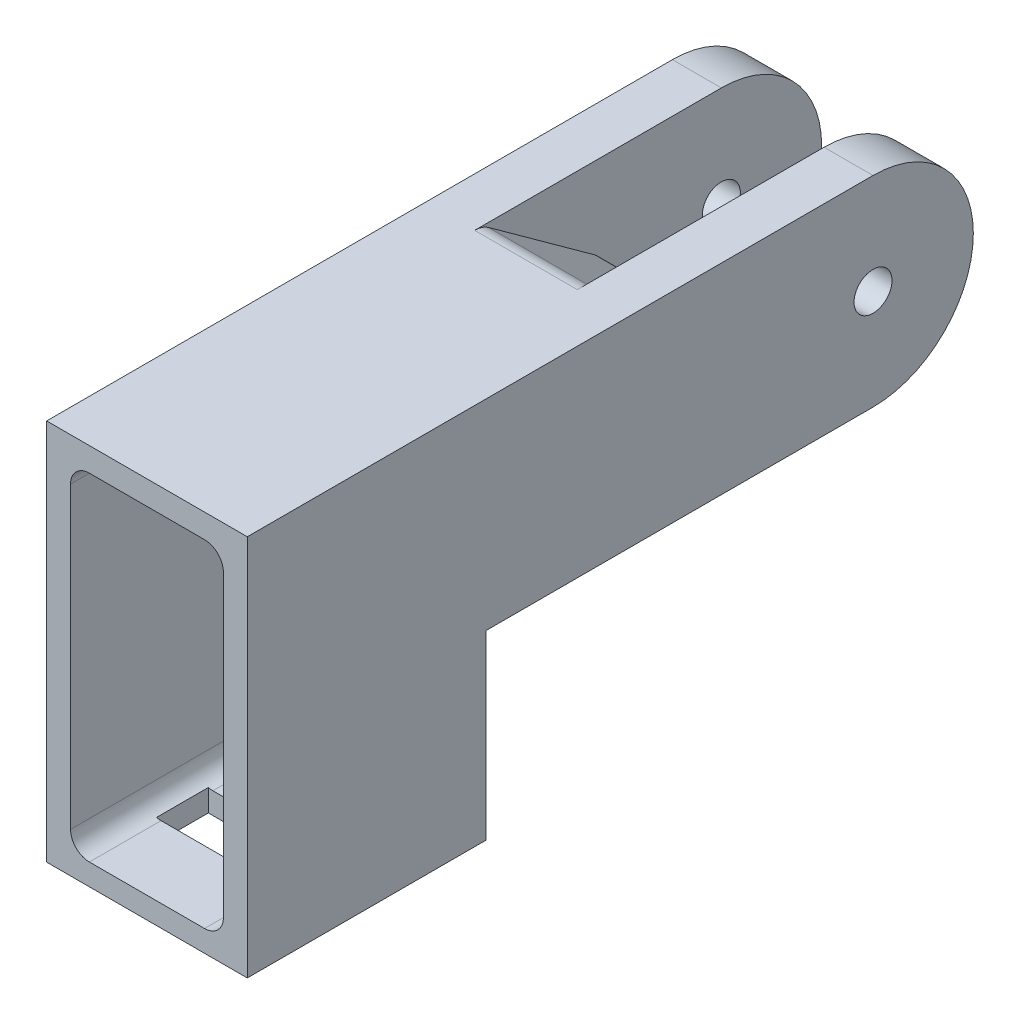
SolidWorks part; units mm, degrees
ref_plane "Front Plane" through (0, 0, 0) normal (0, 0, 1) x (1, 0, 0)
ref_plane "Top Plane" through (0, 0, 0) normal (0, 1, 0) x (1, 0, 0)
ref_plane "Right Plane" through (0, 0, 0) normal (1, 0, 0) x (0, 0, -1)
sketch "Sketch2" plane through (0, 0, 0) normal (0, 0, 1) x (1, 0, 0)
  line L1 (-21, 21) -> (21, 21)
  line L2 (-21, 21) -> (-21, -21)
  line L3 (-21, -21) -> (21, -21)
  line L4 (21, 21) -> (21, -21)
  line L5 (-21, 21) -> (21, -21) construction
  line L6 (-21, -21) -> (21, 21) construction
  point P0 (0, 0)
  dimension "D1" = 42
  dimension "D2" = 42
extrude "Boss-Extrude1" add sketch "Sketch2" along normal blind 60
ref_plane "Plane1" through (0, 0, 0) normal (0, 0, -1) x (-1, 0, 0)
sketch "Sketch3" plane through (0, 0, 0) normal (0, 0, -1) x (-1, 0, 0)
  line L0 (-21, 21) -> (21, 21) construction
  line L1 (21, -21) -> (10.75, -21)
  line L2 (21, -21) -> (21, 21)
  line L3 (21, 21) -> (10.75, 21)
  line L4 (10.75, -21) -> (10.75, 21)
  line L6 (-21, -21) -> (-10.75, -21)
  line L7 (-21, -21) -> (-21, 21)
  line L8 (-21, 21) -> (-10.75, 21)
  line L9 (-10.75, -21) -> (-10.75, 21)
  dimension "D1" = 10.25
  dimension "D2" = 10.25
extrude "Boss-Extrude2" add sketch "Sketch3" along normal blind 21
ref_plane "Plane2" through (-21, 0, 0) normal (-1, 0, 0) x (0, 0, 1)
sketch "Sketch4" plane through (-21, 0, 0) normal (-1, 0, 0) x (0, 0, 1)
  line L0 (-21, -21) -> (-21, 21)
  arc A0 (-21, -21) -> (-21, 21) centre (-21, 0) cw
  dimension "D1" = 21
extrude "Boss-Extrude3" add sketch "Sketch4" against normal blind 10.25
ref_plane "Plane3" through (21, 0, 0) normal (1, 0, 0) x (0, 0, -1)
sketch "Sketch5" plane through (21, 0, 0) normal (1, 0, 0) x (0, 0, -1)
  line L0 (21, 21) -> (21, -21)
  arc A0 (21, 21) -> (21, -21) centre (21, 0) cw
  dimension "D1" = 21
extrude "Boss-Extrude4" add sketch "Sketch5" against normal blind 10.25
ref_plane "Plane4" through (0, 0, 60) normal (0, 0, 1) x (1, 0, 0)
sketch "Sketch6" plane through (0, 0, 60) normal (0, 0, 1) x (1, 0, 0)
  line L0 (21, 21) -> (-21, 21) construction
  line L1 (-16, 16) -> (16, 16)
  line L2 (-16, 16) -> (-16, -16)
  line L3 (-16, -16) -> (16, -16)
  line L4 (16, 16) -> (16, -16)
  line L5 (-16, 16) -> (16, -16) construction
  line L6 (-16, -16) -> (16, 16) construction
  line L7 (21, -21) -> (21, 21) construction
  point P0 (0, 0)
  dimension "D1" = 5
  dimension "D2" = 5
extrude "Cut-Extrude1" cut sketch "Sketch6" against normal blind 27
ref_plane "Plane5" through (10.75, 0, 0) normal (-1, 0, 0) x (0, 0, 1)
sketch "Sketch7" plane through (10.75, 0, 0) normal (-1, 0, 0) x (0, 0, 1)
  line L0 (0, -21) -> (0, 21) construction
  circle A0 centre (-21, 0) radius 3.975
  dimension "D2" = 7.95
  dimension "D1" = 21
extrude "Cut-Extrude2" cut sketch "Sketch7" against normal through all
ref_plane "Plane6" through (-10.75, 0, 0) normal (1, 0, 0) x (0, 0, -1)
sketch "Sketch9" plane through (-10.75, 0, 0) normal (1, 0, 0) x (0, 0, -1)
  line L0 (0, 21) -> (0, -21) construction
  circle A0 centre (21, 0) radius 3.975
  dimension "D2" = 7.95
  dimension "D1" = 21
extrude "Cut-Extrude3" cut sketch "Sketch9" against normal through all
ref_plane "Plane9" through (10.75, 0, 0) normal (-1, 0, 0) x (0, 0, 1)
sketch "Sketch11" plane through (10.75, 0, 0) normal (-1, 0, 0) x (0, 0, 1)
  line L0 (0, 0) -> (0, 21)
  line L1 (0, 0) -> (0, -21)
  line L2 (0, -21) -> (29.0252, -21)
  line L3 (29.0252, -21) -> (0, 0)
  line L4 (0, -21) -> (0, 21) construction
  line L5 (0, 21) -> (29.0252, 21) construction
  line L6 (29.0252, 21) -> (0, 0) construction
  line L7 (0, 0) -> (0, 21)
  line L8 (0, 0) -> (29.0252, 21)
  line L9 (29.0252, 21) -> (0, 21)
  line M5 (0, -21) -> (0, 21)
extrude "Cut-Extrude5" cut sketch "Sketch11" along normal blind 21.5 contours L8 L9 M5 | L1 L2 L3 region at (10.75, 14, 9.6751)
fillet "Fillet1" radius 5 1 edges at (0, 0, 0)
fillet "Fillet2" radius 5 1 edges at (0, -21, 29.0252)
fillet "Fillet3" radius 5 1 edges at (0, 21, 29.0252)
ref_plane "Plane10" through (0, 0, 60) normal (0, 0, 1) x (1, 0, 0)
sketch "Sketch12" plane through (0, 0, 60) normal (0, 0, 1) x (1, 0, 0)
  line L1 (21, 21) -> (-21, 21)
  line L2 (21, 21) -> (21, -59)
  line L3 (21, -59) -> (-21, -59)
  line L4 (-21, 21) -> (-21, -59)
  dimension "D1" = 80
  dimension "D2" = 42
extrude "Boss-Extrude5" add sketch "Sketch12" along normal blind 50
ref_plane "Plane11" through (0, 0, 110) normal (0, 0, 1) x (1, 0, 0)
sketch "Sketch13" plane through (0, 0, 110) normal (0, 0, 1) x (1, 0, 0)
  line L0 (21, 21) -> (-21, 21) construction
  line L1 (16, 16) -> (-16, 16)
  line L2 (16, 16) -> (16, -54.5)
  line L3 (16, -54.5) -> (-16, -54.5)
  line L4 (-16, 16) -> (-16, -54.5)
  line L6 (21, -59) -> (21, 21) construction
  dimension "D1" = 5
  dimension "D2" = 70.5
  dimension "D3" = 5
extrude "Cut-Extrude7" cut sketch "Sketch13" against normal blind 40.5 contours L4 L3 L2 L1
ref_plane "Plane12" through (0, -59, 0) normal (0, -1, 0) x (-1, 0, 0)
sketch "Sketch14" plane through (0, -59, 0) normal (0, -1, 0) x (-1, 0, 0)
  line L1 (13, -95) -> (-13, -95)
  line L2 (13, -95) -> (13, -84.1524)
  line L3 (13, -84.1524) -> (-13, -84.1524)
  line L4 (-13, -95) -> (-13, -84.1524)
  line L5 (13, -95) -> (-13, -84.1524) construction
  line L6 (13, -84.1524) -> (-13, -95) construction
  line L7 (21, -110) -> (-21, -110) construction
  line L8 (-21, -110) -> (-21, -60) construction
  line L9 (21, -110) -> (21, -60) construction
  point P0 (0, -89.5762)
  point P7 (-13, -89.5762)
  dimension "D1" = 15
  dimension "D2" = 8
  dimension "D3" = 8
extrude "Cut-Extrude8" cut sketch "Sketch14" against normal blind 40.5
ref_plane "Plane13" through (0, 0, 60) normal (0, 0, -1) x (-1, 0, 0)
sketch "Sketch15" plane through (0, 0, 60) normal (0, 0, -1) x (-1, 0, 0)
  line L0 (-21, -59) -> (-21, -21) construction
  line L1 (13, -44) -> (-13, -44)
  line L2 (13, -44) -> (13, -33.42)
  line L3 (13, -33.42) -> (-13, -33.42)
  line L4 (-13, -44) -> (-13, -33.42)
  line L5 (13, -44) -> (-13, -33.42) construction
  line L6 (13, -33.42) -> (-13, -44) construction
  line L7 (21, -21) -> (21, -59) construction
  line L8 (21, -59) -> (-21, -59) construction
  point P0 (0, -38.71)
  dimension "D1" = 8
  dimension "D2" = 8
  dimension "D3" = 10.58
  dimension "D4" = 15
extrude "Cut-Extrude9" cut sketch "Sketch15" against normal blind 40.5
ref_plane "Plane14" through (0, 0, 69.5) normal (0, 0, 1) x (1, 0, 0)
sketch "Sketch16" plane through (0, 0, 69.5) normal (0, 0, 1) x (1, 0, 0)
  circle A0 centre (11.995, 11.995) radius 1.825
  circle A1 centre (-11.995, 11.995) radius 1.825
  circle A2 centre (-11.995, -50.495) radius 1.825
  circle A3 centre (11.995, -50.495) radius 1.825
  dimension "D1" = 3.65
  dimension "D2" = 3.65
  dimension "D9" = 3.65
  dimension "D10" = 3.65
fillet "Fillet4" radius 3.95 4 edges at (-16, -54.5, 89.75) (16, -54.5, 89.75) (-16, 16, 89.75) (16, 16, 89.75)
extrude "Cut-Extrude10" cut sketch "Sketch16" against normal blind 20
